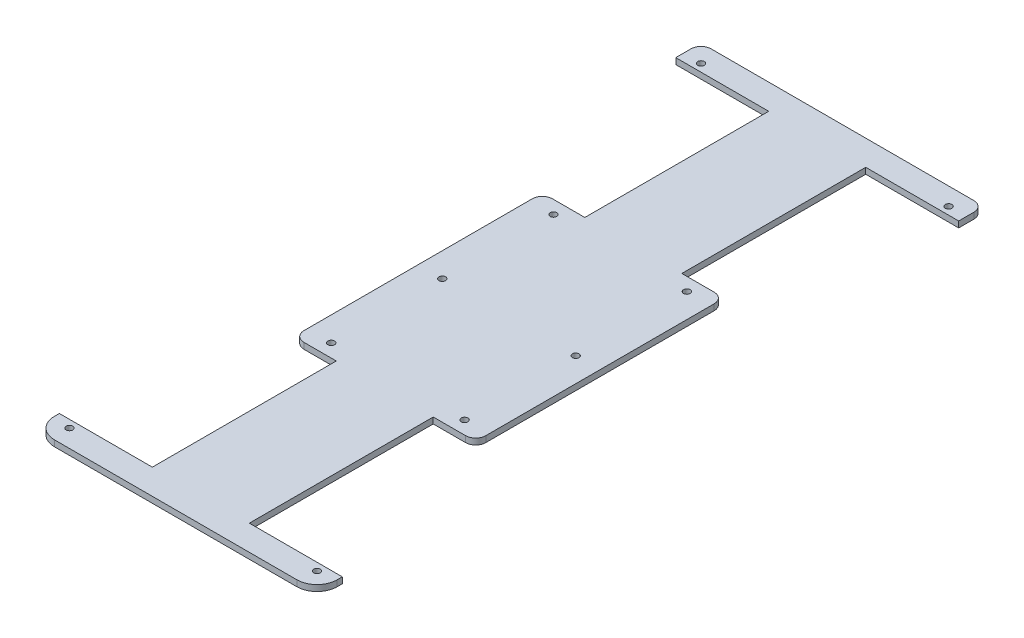
SolidWorks part; units mm, degrees
ref_plane "Front Plane" through (0, 0, 0) normal (0, 0, 1) x (1, 0, 0)
ref_plane "Top Plane" through (0, 0, 0) normal (0, 1, 0) x (1, 0, 0)
ref_plane "Right Plane" through (0, 0, 0) normal (1, 0, 0) x (0, 0, -1)
sketch "Sketch1" plane through (0, 0, 0) normal (0, 1, 0) x (1, 0, 0)
  line L0 (0, 0) -> (140, 0)
  line L1 (0, 0) -> (140, 0) construction
  line L2 (0, 0) -> (0, 330) construction
  line L3 (0, 330) -> (140, 330) construction
  line L4 (140, 0) -> (140, 330) construction
  line L5 (140, 0) -> (140, 12.5)
  line L6 (140, 12.5) -> (94, 12.5)
  line L7 (94, 12.5) -> (94, 103.5)
  line L11 (94, 226.5) -> (94, 317.5)
  line L12 (94, 317.5) -> (140, 317.5)
  line L13 (140, 317.5) -> (140, 330)
  line L14 (140, 330) -> (0, 330)
  line L15 (0, 330) -> (0, 317.5)
  line L16 (0, 317.5) -> (46, 317.5)
  line L17 (46, 317.5) -> (46, 226.5)
  line L21 (46, 103.5) -> (46, 12.5)
  line L22 (46, 12.5) -> (0, 12.5)
  line L23 (0, 12.5) -> (0, 0)
  line L24 (46, 226.5) -> (25, 226.5)
  line L25 (25, 226.5) -> (25, 103.5)
  line L26 (25, 103.5) -> (46, 103.5)
  line L27 (94, 226.5) -> (115, 226.5)
  line L28 (115, 226.5) -> (115, 103.5)
  line L29 (115, 103.5) -> (94, 103.5)
  dimension "D1" = 140
  dimension "D2" = 330
  dimension "D3" = 46
  dimension "D4" = 91
  dimension "D5" = 25
  dimension "D6" = 123
extrude "Boss-Extrude1" add sketch "Sketch1" along normal blind 3
fillet "Fillet1" radius 10 2 edges at (140, 1.5, 0) (0, 1.5, 0)
fillet "Fillet2" radius 5 6 edges at (0, 1.5, -330) (140, 1.5, -330) (115, 1.5, -226.5) (115, 1.5, -103.5) (25, 1.5, -103.5) (25, 1.5, -226.5)
sketch "Sketch2" plane through (0, 3, 0) normal (0, 1, 0) x (1, 0, 0)
  line L2 (37, 220) -> (37, 110) construction
  line L3 (25, 165) -> (37, 165) construction
  line L4 (25, 221.5) -> (25, 108.5) construction
  line L5 (70, 330) -> (70, 0) construction
  line L6 (135, 330) -> (5, 330) construction
  line L7 (10, 0) -> (130, 0) construction
  circle A0 centre (37, 220) radius 1.65
  circle A1 centre (37, 165) radius 1.65
  circle A2 centre (37, 110) radius 1.65
  circle A3 centre (103, 110) radius 1.65
  circle A4 centre (103, 165) radius 1.65
  circle A5 centre (103, 220) radius 1.65
  dimension "D3" = 3.3
  dimension "D1" = 12
  dimension "D2" = 110
extrude "Cut-Extrude1" cut sketch "Sketch2" against normal through all
sketch "Sketch3" plane through (0, 3, 0) normal (0, 1, 0) x (1, 0, 0)
  line L0 (0, 12.5) -> (8.75, 12.5) construction
  line L1 (46, 12.5) -> (0, 12.5) construction
  line L2 (8.75, 12.5) -> (8.75, 8.75) construction
  line L3 (70, 0) -> (70, 57.6288) construction
  line L4 (10, 0) -> (130, 0) construction
  circle A0 centre (8.75, 8.75) radius 1.65
  circle A1 centre (131.25, 8.75) radius 1.65
  dimension "D3" = 3.3
  dimension "D1" = 8.75
  dimension "D2" = 3.75
extrude "Cut-Extrude2" cut sketch "Sketch3" against normal through all
sketch "Sketch4" plane through (0, 3, 0) normal (0, 1, 0) x (1, 0, 0)
  line L0 (0, 317.5) -> (8.75, 317.5) construction
  line L1 (0, 317.5) -> (46, 317.5) construction
  line L2 (8.75, 317.5) -> (8.75, 321.25) construction
  line L3 (70, 330) -> (70, 288.2737) construction
  line L4 (135, 330) -> (5, 330) construction
  circle A0 centre (8.75, 321.25) radius 1.65
  circle A1 centre (131.25, 321.25) radius 1.65
  dimension "D3" = 3.3
  dimension "D1" = 8.75
  dimension "D2" = 3.75
extrude "Cut-Extrude3" cut sketch "Sketch4" against normal through all
